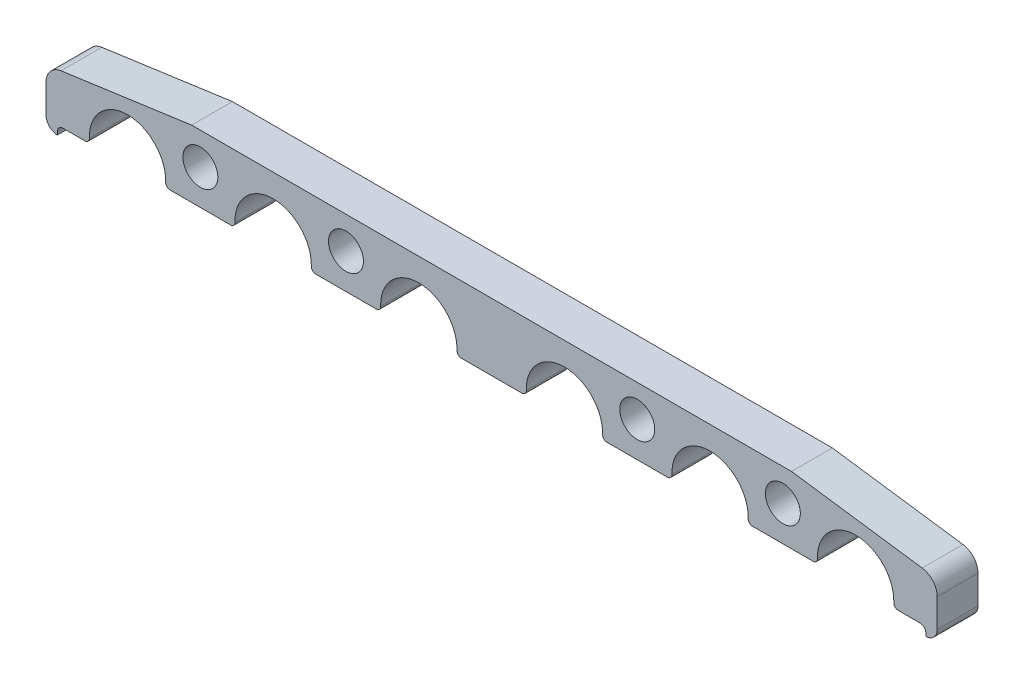
SolidWorks part; units mm, degrees
ref_plane "Plan de face" through (0, 0, 0) normal (0, 0, 1) x (1, 0, 0)
ref_plane "Plan de dessus" through (0, 0, 0) normal (0, 1, 0) x (1, 0, 0)
ref_plane "Plan de droite" through (0, 0, 0) normal (1, 0, 0) x (0, 0, -1)
sketch "Esquisse1" plane through (0, 0, 0) normal (0, 0, 1) x (1, 0, 0)
  line L1 (0, 0) -> (306, 0)
  line L2 (0, 0) -> (0, 26)
  line L3 (0, 26) -> (306, 26)
  line L4 (306, 0) -> (306, 26)
  dimension "D1" = 306
  dimension "D2" = 26
extrude "Boss.-Extru.1" add sketch "Esquisse1" along normal blind 14
sketch "Esquisse2" plane through (0, 0, 14) normal (0, 0, 1) x (1, 0, 0)
  line L0 (153, 3) -> (153, 26) construction
  line L1 (0, 0) -> (306, 0) construction
  line L3 (215.0536, 3) -> (190.9464, 3)
  line L4 (265.0536, 3) -> (240.9464, 3)
  line L5 (165.0536, 3) -> (140.9464, 3)
  line L7 (290.9464, 3) -> (302.1, 3)
  line L8 (302.1, 3) -> (302.1, 0)
  line L10 (302.1, 0) -> (3.9, 0)
  line L11 (3.9, 3) -> (3.9, 0)
  line L12 (15.0536, 3) -> (3.9, 3)
  line L13 (40.9464, 3) -> (65.0536, 3)
  line L14 (90.9464, 3) -> (115.0536, 3)
  line L16 (140.9464, 3) -> (128, 5) construction
  line L17 (128, 5) -> (128, 3) construction
  line L18 (128, 3) -> (140.9464, 3) construction
  line L19 (128, 5) -> (78, 5) construction
  line L20 (78, 5) -> (28, 5) construction
  line L21 (306, 26) -> (0, 26) construction
  arc A0 (165.0536, 3) -> (190.9464, 3) centre (178, 5) cw
  arc A1 (215.0536, 3) -> (240.9464, 3) centre (228, 5) cw
  arc A2 (265.0536, 3) -> (290.9464, 3) centre (278, 5) cw
  arc A3 (40.9464, 3) -> (15.0536, 3) centre (28, 5) ccw
  arc A4 (90.9464, 3) -> (65.0536, 3) centre (78, 5) ccw
  arc A5 (140.9464, 3) -> (115.0536, 3) centre (128, 5) ccw
  point P41 (153, 3)
  dimension "D1" = 13.1
  dimension "D2" = 2
  dimension "D3" = 50
  dimension "D4" = 24.1
  dimension "D5" = 50
  dimension "D6" = 3
extrude "Enlèv. mat.-Extru.1" cut sketch "Esquisse2" against normal blind 14.1
fillet "Congé1" radius 1.5 12 edges at (290.9464, 3, 7) (265.0536, 3, 7) (240.9464, 3, 7) (215.0536, 3, 7) (190.9464, 3, 7) (165.0536, 3, 7) (140.9464, 3, 7) (115.0536, 3, 7) (90.9464, 3, 7) (65.0536, 3, 7) (40.9464, 3, 7) (15.0536, 3, 7)
fillet "Congé2" radius 2 2 edges at (3.9, 3, 7) (302.1, 3, 7)
sketch "Esquisse3" plane through (0, 0, 14) normal (0, 0, 1) x (1, 0, 0)
  line L0 (0, 19) -> (50, 26)
  line L1 (0, 26) -> (0, 0) construction
  line L2 (306, 26) -> (0, 26) construction
  line L3 (50, 26) -> (0, 26)
  line L4 (0, 26) -> (0, 19)
  line L5 (153, 0) -> (153, 26) construction
  line L8 (306, 26) -> (306, 19)
  line L9 (256, 26) -> (306, 26)
  line L10 (306, 19) -> (256, 26)
  dimension "D1" = 50
  dimension "D2" = 7
extrude "Enlèv. mat.-Extru.2" cut sketch "Esquisse3" against normal through all both and the other way through all
fillet "Congé3" radius 6 2 edges at (0, 19, 7) (306, 19, 7)
fillet "Congé4" radius 4 2 edges at (306, 0, 7) (0, 0, 7)
sketch "Esquisse4" plane through (0, 0, 0) normal (0, 0, -1) x (-1, 0, 0)
  line L0 (-153, 26) -> (-153, 0) construction
  line L1 (-256, 26) -> (-50, 26) construction
  line L3 (-153, 14.5) -> (-133.3709, 14.5) construction
  circle A0 centre (-153, 20.5) radius 2.95
  circle A1 centre (-153, 8.5) radius 2.95
  dimension "D1" = 5.9
  dimension "D2" = 12
  dimension "D3" = 5.5
extrude "Enlèv. mat.-Extru.3" cut sketch "Esquisse4" against normal blind 10 and the other way through all
sketch "Esquisse6" plane through (0, 3, 0) normal (0, -1, 0) x (1, 0, 0)
  line L0 (153, 0) -> (153, 14) construction
  line L2 (163.4086, 14) -> (142.5914, 14) construction
  line L3 (153, 7) -> (298, 7) construction
  line L4 (103, 0) -> (103, 14) construction
  line L6 (113.4086, 14) -> (92.5914, 14) construction
  line L7 (203, 0) -> (203, 14) construction
  line L9 (142.5914, 0) -> (163.4086, 0) construction
  circle A1 centre (298, 7) radius 2.15
  circle A2 centre (8, 7) radius 2.15
  circle A3 centre (103, 7) radius 2.15
  circle A4 centre (203, 7) radius 2.15
  dimension "D1" = 4.3
  dimension "D2" = 290
  dimension "D3" = 7
extrude "Enlèv. mat.-Extru.5" cut sketch "Esquisse6" against normal blind 5.5
sketch "Esquisse7" plane through (0, 0, 14) normal (0, 0, 1) x (1, 0, 0)
  line L0 (53, 3) -> (53, 15) construction
  line L2 (53, 15) -> (103, 15) construction
  line L3 (103, 15) -> (103, 3) construction
  line L4 (113.4086, 3) -> (92.5914, 3) construction
  line L5 (153, 3) -> (153, 40.9453) construction
  line L6 (163.4086, 3) -> (142.5914, 3) construction
  line L7 (203, 15) -> (203, 3) construction
  line L8 (253, 15) -> (203, 15) construction
  line L9 (253, 3) -> (253, 15) construction
  line L10 (63.4086, 3) -> (42.5914, 3) construction
  circle A0 centre (53, 15) radius 6
  circle A1 centre (103, 15) radius 6
  circle A2 centre (203, 15) radius 6
  circle A3 centre (253, 15) radius 6
  dimension "D1" = 12
  dimension "D2" = 12
extrude "Enlèv. mat.-Extru.6" cut sketch "Esquisse7" against normal through all both and the other way through all
sketch "Esquisse8" plane through (0, 0, 0) normal (0, 0, -1) x (-1, 0, 0)
  circle A0 centre (-153, 20.5) radius 3.65
  circle A1 centre (-153, 8.5) radius 3.65
  dimension "D1" = 7.3
extrude "Enlèv. mat.-Extru.7" cut sketch "Esquisse8" against normal blind 1.3
